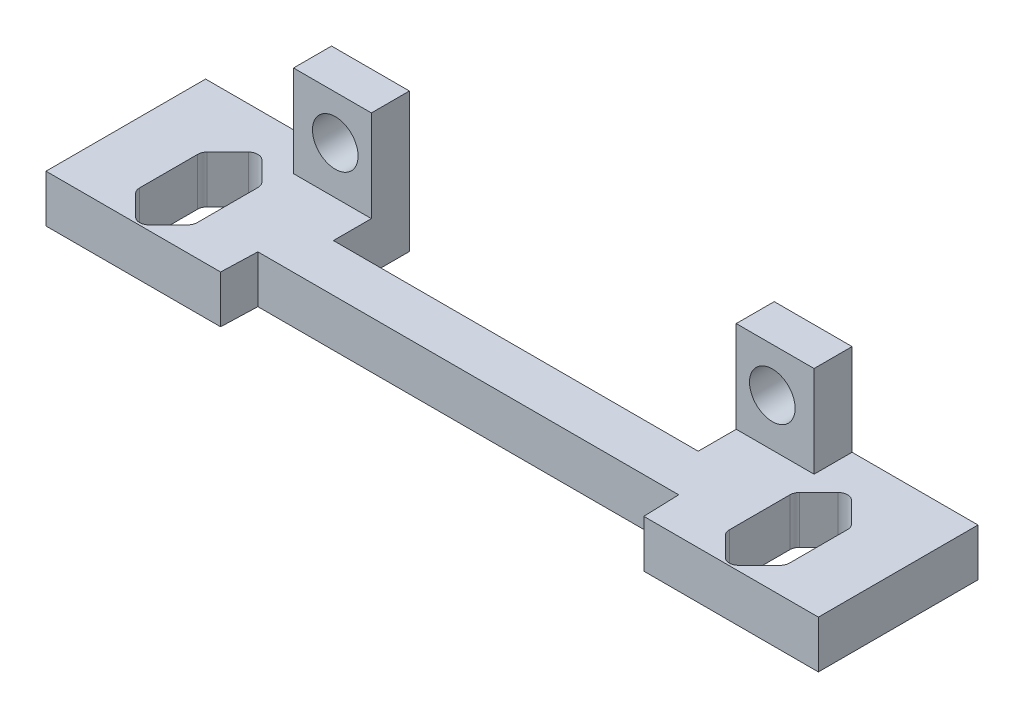
SolidWorks part; units mm, degrees
ref_plane "前视基准面" through (0, 0, 0) normal (0, 0, 1) x (1, 0, 0)
ref_plane "上视基准面" through (0, 0, 0) normal (0, 1, 0) x (1, 0, 0)
ref_plane "右视基准面" through (0, 0, 0) normal (1, 0, 0) x (0, 0, -1)
sketch "参考面" plane through (0, 0, 0) normal (0, 1, 0) x (1, 0, 0)
  line L0 (0, 17.1678) -> (0, -7.9399) construction
  line L1 (-14.1474, -13.5693) -> (-15.2326, -12.4841)
  line L2 (-15.9397, -12.4841) -> (-16.9545, -13.499)
  line L3 (-11.3955, -31.9433) -> (-10.3849, -1.2232)
  line L4 (-10.5767, -38.0268) -> (-5.85, -43.5)
  line L5 (-5.85, -43.5) -> (5.85, -43.5)
  line L6 (-11.3974, -35.8209) -> (-11.3974, -32.0543)
  line L7 (-9.5, 0) -> (9.5, 0)
  line L8 (10.5767, -38.0268) -> (5.85, -43.5)
  line L9 (11.3974, -35.8209) -> (11.3974, -32.0543)
  line L10 (11.3955, -31.9433) -> (10.3849, -1.2232)
  line L11 (-16.9545, -22.7061) -> (-15.8693, -23.7913)
  line L12 (-15.1622, -23.7913) -> (-14.1474, -22.7764)
  line L13 (-17.1009, -13.8525) -> (-17.1009, -22.3525)
  line L14 (-14.0009, -13.9229) -> (-14.0009, -16.9775)
  line L15 (-14.0009, -16.9775) -> (-14.5009, -17.4775)
  line L16 (-14.5009, -17.4775) -> (-14.5009, -18.7275)
  line L17 (-14.5009, -18.7275) -> (-14.0009, -19.2275)
  line L18 (-14.0009, -19.2275) -> (-14.0009, -22.4229)
  line L19 (14.5009, -18.7275) -> (14.0009, -19.2275)
  line L20 (14.5009, -17.4775) -> (14.5009, -18.7275)
  line L21 (14.0009, -16.9775) -> (14.5009, -17.4775)
  line L22 (14.0009, -13.9229) -> (14.0009, -16.9775)
  line L23 (14.1474, -13.5693) -> (15.2326, -12.4841)
  line L24 (15.9397, -12.4841) -> (16.9545, -13.499)
  line L25 (17.1009, -13.8525) -> (17.1009, -22.3525)
  line L26 (16.9545, -22.7061) -> (15.8693, -23.7913)
  line L27 (15.1622, -23.7913) -> (14.1474, -22.7764)
  line L28 (14.0009, -19.2275) -> (14.0009, -22.4229)
  arc A0 (-14.0009, -13.9229) -> (-14.1474, -13.5693) centre (-14.5009, -13.9229) ccw
  arc A1 (-15.2326, -12.4841) -> (-15.9397, -12.4841) centre (-15.5861, -12.8377) ccw
  arc A2 (-17.1009, -13.8525) -> (-16.9545, -13.499) centre (-16.6009, -13.8525) cw
  arc A3 (-9.5, 0) -> (-10.3849, -1.2232) centre (-9.0356, -1.2676) ccw
  arc A4 (-11.3974, -32.0543) -> (-11.3955, -31.9433) centre (-8.0224, -32.0543) cw
  arc A5 (-10.5767, -38.0268) -> (-11.3974, -35.8209) centre (-8.0224, -35.8209) cw
  arc A6 (10.5767, -38.0268) -> (11.3974, -35.8209) centre (8.0224, -35.8209) ccw
  arc A7 (11.3974, -32.0543) -> (11.3955, -31.9433) centre (8.0224, -32.0543) ccw
  arc A8 (9.5, 0) -> (10.3849, -1.2232) centre (9.0356, -1.2676) cw
  arc A9 (-17.1009, -22.3525) -> (-16.9545, -22.7061) centre (-16.6009, -22.3525) ccw
  arc A10 (-15.8693, -23.7913) -> (-15.1622, -23.7913) centre (-15.5157, -23.4377) ccw
  arc A11 (-14.0009, -22.4229) -> (-14.1474, -22.7764) centre (-14.5009, -22.4229) cw
  arc A12 (14.0009, -13.9229) -> (14.1474, -13.5693) centre (14.5009, -13.9229) cw
  arc A13 (15.2326, -12.4841) -> (15.9397, -12.4841) centre (15.5861, -12.8377) cw
  arc A14 (17.1009, -13.8525) -> (16.9545, -13.499) centre (16.6009, -13.8525) ccw
  arc A15 (17.1009, -22.3525) -> (16.9545, -22.7061) centre (16.6009, -22.3525) cw
  arc A16 (15.8693, -23.7913) -> (15.1622, -23.7913) centre (15.5157, -23.4377) cw
  arc A17 (14.0009, -22.4229) -> (14.1474, -22.7764) centre (14.5009, -22.4229) ccw
  point P32 (-11.0823, -22.4229)
  point P49 (0, -43.5)
  point P58 (0, 0)
sketch "草图2" plane through (0, 0, 0) normal (0, 1, 0) x (1, 0, 0)
  line L2 (11.3955, -31.9433) -> (10.3849, -1.2232) construction
  line L4 (11.1361, -24.0562) -> (20.3239, -24.0562)
  line L11 (14.0009, -19.2275) -> (14.0009, -22.4229)
  line L12 (14.1474, -22.7764) -> (15.1622, -23.7913)
  line L13 (16.9545, -22.7061) -> (15.8693, -23.7913)
  line L15 (-11.1361, -24.0562) -> (-20.3239, -24.0562)
  line L21 (0, 2.8472) -> (0, -12.4841) construction
  line L22 (0, 17.1678) -> (0, -7.9399) construction
  line L26 (16.9545, -18.9443) -> (15.8693, -17.8591)
  line L30 (-14.0009, -19.2275) -> (-14.0009, -22.4229)
  line L34 (-16.9545, -22.7061) -> (-15.8693, -23.7913)
  line L35 (-14.1474, -22.7764) -> (-15.1622, -23.7913)
  line L36 (-10.8621, -15.6567) -> (-9.6, -15.6567)
  line L37 (-9.6, -15.6567) -> (-9.6, -22.1567)
  line L38 (-9.6, -22.1567) -> (-11.0736, -22.1567)
  line L39 (9.6, -22.1567) -> (11.0736, -22.1567)
  line L40 (9.6, -15.6567) -> (9.6, -22.1567)
  line L41 (10.8621, -15.6567) -> (9.6, -15.6567)
  line L42 (-11.0736, -22.1567) -> (-11.1361, -24.0562)
  line L43 (11.0736, -22.1567) -> (11.1361, -24.0562)
  line L44 (-10.8621, -15.6567) -> (-14.0009, -15.6567)
  line L45 (-17.1009, -15.6567) -> (-20.3239, -15.6567)
  line L46 (-20.3239, -24.0562) -> (-20.3239, -15.6567)
  line L49 (10.8621, -15.6567) -> (14.0009, -15.6567)
  line L50 (20.3239, -15.6567) -> (17.1009, -15.6567)
  line L51 (20.3239, -15.6567) -> (20.3239, -24.0562)
  line L54 (-17.1009, -22.3525) -> (-17.1009, -19.2979)
  line L55 (-17.1009, -13.8525) -> (-17.1009, -22.3525) construction
  line L56 (-17.531, -20.8252) -> (-12.875, -20.8252) construction
  line L57 (-14.1474, -18.874) -> (-15.1622, -17.8591)
  line L58 (-16.9545, -18.9443) -> (-15.8693, -17.8591)
  line L59 (-17.1009, -15.6567) -> (-14.0009, -15.6567)
  line L60 (17.5016, -20.8252) -> (13.274, -20.8252) construction
  line L61 (14.1474, -18.874) -> (15.1622, -17.8591)
  line L62 (17.1009, -19.2979) -> (17.1009, -22.3525)
  line L63 (14.0009, -15.6567) -> (17.1009, -15.6567)
  arc A0 (14.0009, -22.4229) -> (14.1474, -22.7764) centre (14.5009, -22.4229) ccw
  arc A1 (15.1622, -23.7913) -> (15.8693, -23.7913) centre (15.5157, -23.4377) ccw
  arc A2 (17.1009, -22.3525) -> (16.9545, -22.7061) centre (16.6009, -22.3525) cw
  arc A9 (-17.1009, -22.3525) -> (-16.9545, -22.7061) centre (-16.6009, -22.3525) ccw
  arc A10 (-15.8693, -23.7913) -> (-15.1622, -23.7913) centre (-15.5157, -23.4377) ccw
  arc A11 (-14.0009, -22.4229) -> (-14.1474, -22.7764) centre (-14.5009, -22.4229) cw
  arc A12 (-15.8693, -17.8591) -> (-15.1622, -17.8591) centre (-15.5157, -18.2127) cw
  arc A13 (-14.0009, -19.2275) -> (-14.1474, -18.874) centre (-14.5009, -19.2275) ccw
  arc A14 (-17.1009, -19.2979) -> (-16.9545, -18.9443) centre (-16.6009, -19.2979) cw
  arc A15 (17.1009, -19.2979) -> (16.9545, -18.9443) centre (16.6009, -19.2979) ccw
  arc A16 (15.1622, -17.8591) -> (15.8693, -17.8591) centre (15.5157, -18.2127) cw
  arc A17 (14.0009, -19.2275) -> (14.1474, -18.874) centre (14.5009, -19.2275) cw
  dimension "D1" = 19.2
  dimension "D2" = 6.5
extrude "连接件固定位" add sketch "草图2" along normal blind 2.5
sketch "草图3" plane through (0, 0, 15.6567) normal (0, 0, -1) x (-1, 0, 0)
  line L0 (0, 6.8267) -> (0, -3.5616) construction
  line L1 (-9.6, 2.5) -> (-13.6968, 2.5)
  line L2 (-9.6, 2.5) -> (-9.6, 7.3177)
  line L3 (-9.6, 7.3177) -> (-13.6968, 7.3177)
  line L4 (-13.6968, 2.5) -> (-13.6968, 7.3177)
  line L5 (9.6, 7.3177) -> (13.6968, 7.3177)
  line L6 (13.6968, 2.5) -> (13.6968, 7.3177)
  line L7 (9.6, 2.5) -> (13.6968, 2.5)
  line L8 (9.6, 2.5) -> (9.6, 7.3177)
  circle A0 centre (-11.5, 5) radius 1.2
  circle A1 centre (11.5, 5) radius 1.2
  dimension "D1" = 2.4
  dimension "D2" = 23
  dimension "D3" = 2.5
extrude "凸台-拉伸1" add sketch "草图3" against normal blind 2
sketch "草图5" plane through (9.6, 0, 0) normal (-1, 0, 0) x (0, 0, 1)
  line L0 (17.6567, 2.5) -> (22.1567, 2.5) construction
  line L1 (22.1567, 0) -> (19.6567, 0)
  line L2 (22.1567, 0) -> (22.1567, 2.5)
  line L3 (22.1567, 2.5) -> (19.6567, 2.5)
  line L4 (19.6567, 0) -> (19.6567, 2.5)
  line L5 (17.6567, 2.5) -> (17.6567, 7.3177) construction
  dimension "D1" = 2
extrude "凸台-拉伸2" add sketch "草图5" along normal up to next
